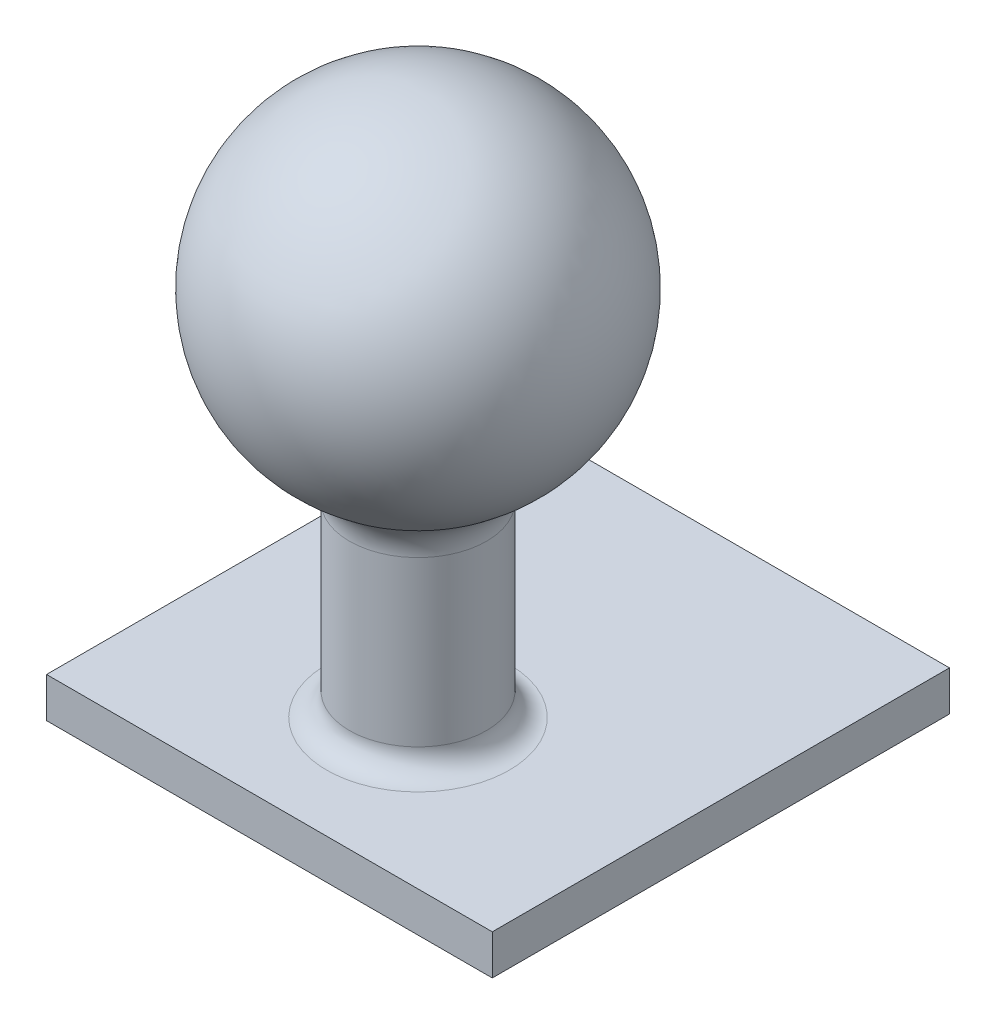
SolidWorks part; units mm, degrees
material "UNOBTANIUM"
ref_plane "Top Plane" through (0, 0, 0) normal (0, 0, 1) x (1, 0, 0)
ref_plane "Right Plane" through (0, 0, 0) normal (0, 1, 0) x (1, 0, 0)
ref_plane "Front Plane" through (0, 0, 0) normal (1, 0, 0) x (0, 0, -1)
ref_axis "x-axis" through (-11, 0, 0) along (1, 0, 0)
ref_axis "y-axis" through (0, -19.275, 0) along (0, 1, 0)
ref_axis "z-axis" through (0, 0, 8.55) along (0, 0, -1)
sketch "Sketch1" plane through (0, 0, 0) normal (1, 0, 0) x (0, 0, -1)
  line L0 (0, 0) -> (0, -36) construction
  line L1 (3, -6.8739) -> (3, -16.25)
  line L2 (3, -16.25) -> (6, -16.25)
  line L3 (6, -16.25) -> (6, -18)
  line L4 (6, -18) -> (0, -18)
  line L5 (0, -18) -> (0, -7.5)
  line L6 (0, 0) -> (0, 7.5) construction
  line L7 (0, 7.5) -> (0, -7.5)
  arc A0 (3, -6.8739) -> (0, 7.5) centre (0, 0) ccw
  dimension "D1" = 15
  dimension "D2" = 6
  dimension "D3" = 1.75
  dimension "D4" = 6
  dimension "D5" = 18
revolve "Revolve1" add sketch "Sketch1" angle 360 about L0
sketch "Sketch2" plane through (0, -18, 0) normal (0, -1, 0) x (1, 0, 0)
  line L1 (-9.75, -10) -> (9.75, -10)
  line L2 (-9.75, -10) -> (-9.75, 10)
  line L3 (-9.75, 10) -> (9.75, 10)
  line L4 (9.75, -10) -> (9.75, 10)
  line L5 (-9.75, -10) -> (9.75, 10) construction
  line L6 (-9.75, 10) -> (9.75, -10) construction
  point P0 (0, 0)
  dimension "D1" = 19.5
  dimension "D2" = 20
extrude "Boss-Extrude1" add sketch "Sketch2" against normal up to surface (1.75 mm away) up to face at (0, -16.25, 3)
sketch "Sketch3" plane through (0, -16.25, 0) normal (0, 1, 0) x (1, 0, 0)
  line L0 (9.75, -10) -> (9.75, 10) construction
  line L1 (-9.75, -10) -> (9.75, -10)
  line L2 (-9.75, -10) -> (-9.75, -6.5)
  line L3 (-9.75, -6.5) -> (9.75, -6.5)
  line L4 (9.75, -10) -> (9.75, -6.5)
  dimension "D1" = 3.5
extrude "Cut-Extrude1" cut sketch "Sketch3" against normal through all
sketch "Sketch4" plane through (0, 0, -10) normal (0, 0, -1) x (-1, 0, 0)
  line L4 (9.75, -16.25) -> (-9.75, -16.25)
  line L5 (-9.75, -16.25) -> (-9.75, -18)
  line L6 (-9.75, -18) -> (9.75, -18)
  line L7 (9.75, -18) -> (9.75, -16.25)
  line L8 (9.75, -16.25) -> (-9.75, -16.25)
  line L9 (-9.75, -16.25) -> (-9.75, -18)
  line L10 (-9.75, -18) -> (9.75, -18)
  line L11 (9.75, -18) -> (9.75, -16.25)
  dimension "D1" = 0
extrude "Boss-Extrude2" add sketch "Sketch4" along normal blind 3.5
fillet "Fillet1" radius 2 1 edges at (0, -6.8739, 3)
fillet "Fillet2" radius 1 1 edges at (0, -16.25, 3)
